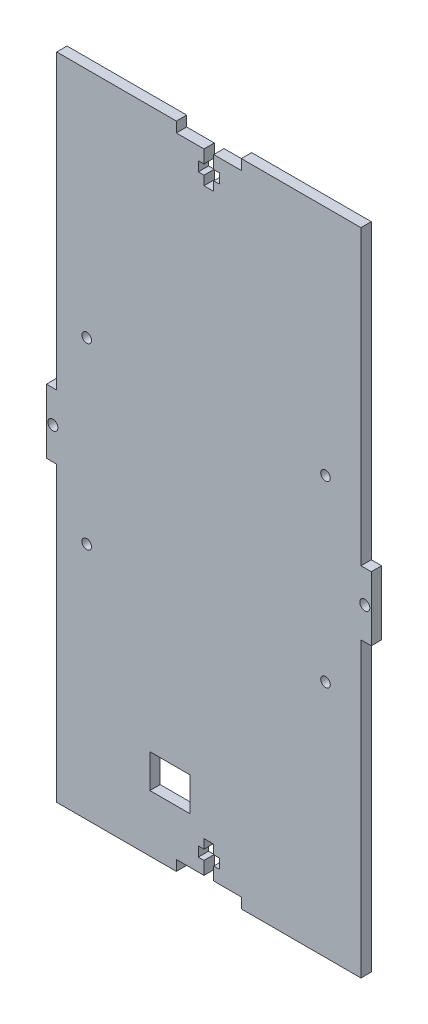
SolidWorks part; units mm, degrees
ref_plane "Front Plane" through (0, 0, 0) normal (0, 0, 1) x (1, 0, 0)
ref_plane "Top Plane" through (0, 0, 0) normal (0, 1, 0) x (1, 0, 0)
ref_plane "Right Plane" through (0, 0, 0) normal (1, 0, 0) x (0, 0, -1)
sketch "Sketch1" plane through (0, 0, 0) normal (0, 0, 1) x (1, 0, 0)
  line L0 (0, 40) -> (0, -40) construction
  line L5 (-50, -100) -> (50, 100) construction
  line L6 (-50, 100) -> (50, -100) construction
  line L7 (-100, 0) -> (100, 0) construction
  line L32 (-50, 100) -> (50, 100)
  line L35 (50, 100) -> (50, -100)
  line L36 (50, -100) -> (-50, -100)
  line L37 (-50, -100) -> (-50, 100)
  point P0 (0, 0)
  dimension "D1" = 100
  dimension "D2" = 200
extrude "Boss-Extrude2" add sketch "Sketch1" along normal blind 3.18
sketch "Sketch2" plane through (0, 0, 3.18) normal (0, 0, 1) x (1, 0, 0)
  line L0 (0, -100) -> (0, 100) construction
  line L1 (-123.0225, 0) -> (147.0753, 0) construction
  line L2 (50, 100) -> (-50, 100) construction
  line L4 (-10, 100) -> (-10, 96.82)
  line L5 (-10, 96.82) -> (-1.5, 96.82)
  line L6 (10, 100) -> (10, 96.82)
  line L7 (1.5, 96.82) -> (10, 96.82)
  line L9 (-1.5, 96.82) -> (-1.5, 92.82)
  line L10 (-1.5, 87) -> (1.5, 87)
  line L11 (1.5, 96.82) -> (1.5, 92.82)
  line L12 (-3.25, 92.82) -> (-1.5, 92.82)
  line L13 (-3.25, 92.82) -> (-3.25, 89.82)
  line L14 (-3.25, 89.82) -> (-1.5, 89.82)
  line L15 (3.25, 92.82) -> (3.25, 89.82)
  line L16 (1.5, 92.82) -> (3.25, 92.82)
  line L17 (-1.5, 89.82) -> (-1.5, 87)
  line L18 (1.5, 89.82) -> (1.5, 87)
  line L19 (1.5, 89.82) -> (3.25, 89.82)
  line L20 (-10, 100) -> (10, 100)
  line L21 (-50, -100) -> (50, -100) construction
  line L22 (-50, 100) -> (-50, -100) construction
  line L23 (-50, 9.875) -> (-46.82, 9.875)
  line L24 (-50, 9.875) -> (-50, 100)
  line L25 (-50, 100) -> (-46.82, 100)
  line L26 (-46.82, 9.875) -> (-46.82, 100)
  line L28 (-50, -9.875) -> (-46.82, -9.875)
  line L29 (-50, -9.875) -> (-50, -100)
  line L30 (-50, -100) -> (-46.82, -100)
  line L31 (-46.82, -9.875) -> (-46.82, -100)
  circle A0 centre (-48, 0) radius 1.55
  dimension "D11" = 3.1
  dimension "D12" = 2
  dimension "D1" = 4
  dimension "D2" = 3
  dimension "D3" = 3
  dimension "D4" = 20
  dimension "D5" = 6.5
  dimension "D6" = 3.18
  dimension "D7" = 13
  dimension "D8" = 19.75
  dimension "D9" = 3.18
  dimension "D10" = 3.18
extrude "Cut-Extrude1" cut sketch "Sketch2" against normal through all
mirror "Mirror1" about plane through (0, 0, 0) normal (0, 1, 0) of "Cut-Extrude1"
mirror "Mirror3" about plane through (0, 0, 0) normal (1, 0, 0) of "Cut-Extrude1"
sketch "Sketch4" plane through (0, 0, 3.18) normal (0, 0, 1) x (1, 0, 0)
  line L5 (-18.15, -82.52) -> (-5.7964, -82.52)
  line L6 (-18.15, -82.52) -> (-18.15, -72.1664)
  line L7 (-18.15, -72.1664) -> (-5.7964, -72.1664)
  line L8 (-5.7964, -82.52) -> (-5.7964, -72.1664)
  arc A0 (-5.65, -72.52) -> (-6.15, -72.02) centre (-6.15, -72.52) ccw construction
extrude "Cut-Extrude3" cut sketch "Sketch4" against normal through all
sketch "Sketch5" plane through (0, 0, 3.18) normal (0, 0, 1) x (1, 0, 0)
  circle A0 centre (-37.5809, 28.4641) radius 1.47
  circle A1 centre (35.9045, 28.4641) radius 1.47
  circle A2 centre (-37.5809, -26.5359) radius 1.47
  circle A3 centre (35.9045, -26.5359) radius 1.47
  circle A4 centre (-37.5809, 28.4641) radius 1.47 construction
  circle A5 centre (35.9045, 28.4641) radius 1.47 construction
  circle A6 centre (35.9045, -26.5359) radius 1.47 construction
  circle A8 centre (-37.5809, -26.5359) radius 1.47 construction
extrude "Cut-Extrude4" cut sketch "Sketch5" against normal through all
